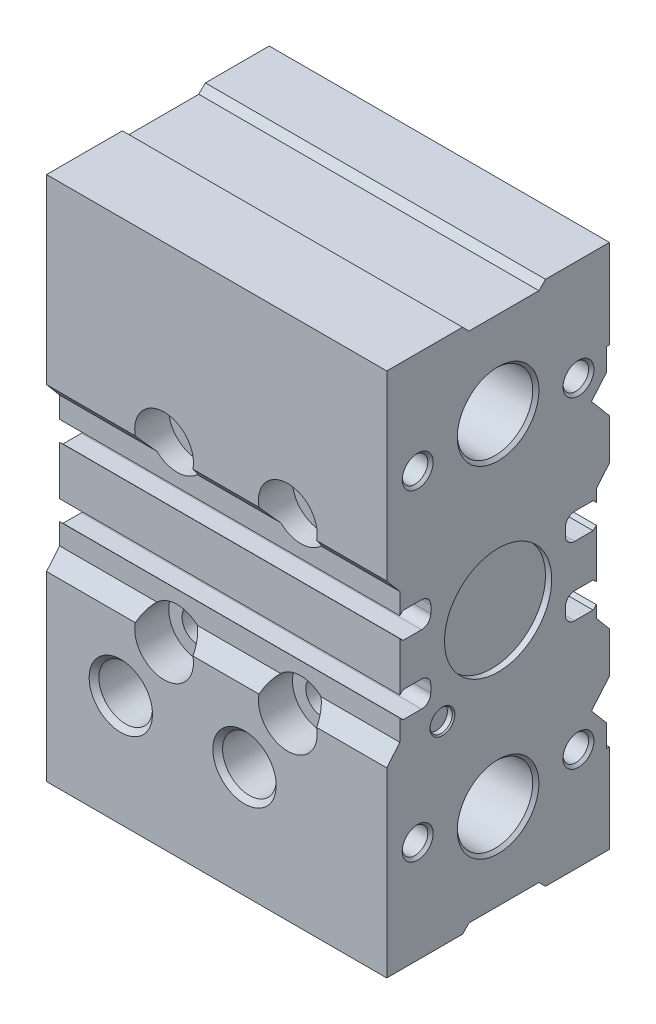
SolidWorks part; units mm, degrees
ref_plane "前视基准面" through (0, 0, 0) normal (0, 0, 1) x (1, 0, 0)
ref_plane "上视基准面" through (0, 0, 0) normal (0, 1, 0) x (1, 0, 0)
ref_plane "右视基准面" through (0, 0, 0) normal (1, 0, 0) x (0, 0, -1)
sketch "草图1" plane through (0, 0, 0) normal (1, 0, 0) x (0, 0, -1)
  line L0 (-18, -42.5) -> (-5.75, -42.5)
  line L1 (-5.75, -42.5) -> (-4.6875, -41.4375)
  line L2 (-4.6875, -41.4375) -> (6.6042, -41.4375)
  line L3 (6.6042, -41.4375) -> (7.6667, -42.5)
  line L4 (7.6667, -42.5) -> (18, -42.5)
  line L5 (18, -42.5) -> (18, -28.1522)
  line L6 (18, -28.1522) -> (17.5, -28.1522)
  line L7 (17.5, -28.1522) -> (17.5, -24.5)
  line L8 (17.5, -24.5) -> (15.1, -21.6667)
  line L9 (15.1, -21.6667) -> (18, -18.2431)
  line L10 (18, -18.2431) -> (18, -11.5959)
  line L11 (18, -11.5959) -> (15.8824, -9.0722)
  line L12 (15.8824, -9.0722) -> (15.8824, -7.1556)
  line L13 (15.3538, -7.6556) -> (12.3824, -7.6556)
  line L14 (10.8824, -6.1556) -> (10.8824, -4.9556)
  line L15 (12.3824, -3.4556) -> (15.3538, -3.4556)
  line L16 (15.8824, -3.9556) -> (15.8824, 3.9556)
  line L17 (15.3538, 3.4556) -> (12.3824, 3.4556)
  line L18 (10.8824, 4.9556) -> (10.8824, 6.1556)
  line L19 (12.3824, 7.6556) -> (15.3538, 7.6556)
  line L20 (15.8824, 7.1556) -> (15.8824, 9.0722)
  line L21 (15.8824, 9.0722) -> (18, 11.5959)
  line L22 (18, 11.5959) -> (18, 18.2431)
  line L23 (18, 18.2431) -> (15.1, 21.6667)
  line L24 (15.1, 21.6667) -> (17.5, 24.5)
  line L25 (17.5, 24.5) -> (17.5, 28.1522)
  line L26 (17.5, 28.1522) -> (18, 28.1522)
  line L27 (18, 28.1522) -> (18, 42.5)
  line L28 (18, 42.5) -> (7.6667, 42.5)
  line L29 (7.6667, 42.5) -> (6.6042, 41.4375)
  line L30 (6.6042, 41.4375) -> (-4.6875, 41.4375)
  line L31 (-4.6875, 41.4375) -> (-5.75, 42.5)
  line L32 (-5.75, 42.5) -> (-18, 42.5)
  line L33 (-18, 42.5) -> (-18, 13.0793)
  line L34 (-18, 13.0793) -> (-15.8824, 10.5556)
  line L35 (-15.8824, 10.5556) -> (-15.8824, 7.1556)
  line L36 (-15.3538, 7.6556) -> (-12.3824, 7.6556)
  line L37 (-10.8824, 6.1556) -> (-10.8824, 4.9556)
  line L38 (-12.3824, 3.4556) -> (-15.3538, 3.4556)
  line L39 (-15.8824, 3.9556) -> (-15.8824, -3.9556)
  line L40 (-15.3538, -3.4556) -> (-12.3824, -3.4556)
  line L41 (-10.8824, -4.9556) -> (-10.8824, -6.1556)
  line L42 (-12.3824, -7.6556) -> (-15.3538, -7.6556)
  line L43 (-15.8824, -7.1556) -> (-15.8824, -10.5556)
  line L44 (-15.8824, -10.5556) -> (-18, -13.0793)
  line L45 (-18, -13.0793) -> (-18, -42.5)
  arc A0 (15.8824, -7.1556) -> (15.3538, -7.6556) centre (13.8681, -5.5556) cw
  arc A1 (12.3824, -7.6556) -> (10.8824, -6.1556) centre (12.3824, -6.1556) cw
  arc A2 (10.8824, -4.9556) -> (12.3824, -3.4556) centre (12.3824, -4.9556) cw
  arc A3 (15.3538, -3.4556) -> (15.8824, -3.9556) centre (13.8681, -5.5556) cw
  arc A4 (15.8824, 3.9556) -> (15.3538, 3.4556) centre (13.8681, 5.5556) cw
  arc A5 (12.3824, 3.4556) -> (10.8824, 4.9556) centre (12.3824, 4.9556) cw
  arc A6 (10.8824, 6.1556) -> (12.3824, 7.6556) centre (12.3824, 6.1556) cw
  arc A7 (15.3538, 7.6556) -> (15.8824, 7.1556) centre (13.8681, 5.5556) cw
  arc A8 (-15.8824, 7.1556) -> (-15.3538, 7.6556) centre (-13.8681, 5.5556) cw
  arc A9 (-12.3824, 7.6556) -> (-10.8824, 6.1556) centre (-12.3824, 6.1556) cw
  arc A10 (-10.8824, 4.9556) -> (-12.3824, 3.4556) centre (-12.3824, 4.9556) cw
  arc A11 (-15.3538, 3.4556) -> (-15.8824, 3.9556) centre (-13.8681, 5.5556) cw
  arc A12 (-15.8824, -3.9556) -> (-15.3538, -3.4556) centre (-13.8681, -5.5556) cw
  arc A13 (-12.3824, -3.4556) -> (-10.8824, -4.9556) centre (-12.3824, -4.9556) cw
  arc A14 (-10.8824, -6.1556) -> (-12.3824, -7.6556) centre (-12.3824, -6.1556) cw
  arc A15 (-15.3538, -7.6556) -> (-15.8824, -7.1556) centre (-13.8681, -5.5556) cw
extrude "凸台-拉伸1" add sketch "草图1" along normal blind 55
sketch "草图2" plane through (0, 0, 0) normal (0, 0, 1) x (1, 0, 0)
  line L0 (0, 27.5) -> (0, 34.1)
  line L1 (0, 34.1) -> (0.5, 33.6)
  line L2 (0.5, 33.6) -> (54.5, 33.6)
  line L3 (54.5, 33.6) -> (55, 34.1)
  line L4 (55, 34.1) -> (55, 27.5)
  line L5 (55, 27.5) -> (0, 27.5)
  line L6 (55, 27.5) -> (0, 27.5) construction
revolve "切除-旋转1" cut sketch "草图2" angle 360 about L6 reverse direction yes
sketch "草图3" plane through (0, 0, 0) normal (0, 0, 1) x (1, 0, 0)
  line L0 (0, -27.5) -> (0, -20.9)
  line L1 (0, -20.9) -> (0.5, -21.4)
  line L2 (0.5, -21.4) -> (54.5, -21.4)
  line L3 (54.5, -21.4) -> (55, -20.9)
  line L4 (55, -20.9) -> (55, -27.5)
  line L5 (55, -27.5) -> (0, -27.5)
  line L6 (55, -27.5) -> (0, -27.5) construction
revolve "切除-旋转2" cut sketch "草图3" angle 360 about L6 reverse direction yes
ref_plane "基准面4" through (0, 14, 0) normal (0, 1, 0) x (1, 0, 0)
ref_plane "基准面5" through (0, 0, 18) normal (0, 0, 1) x (1, 0, 0)
sketch "草图4" plane through (0, 14, 0) normal (0, 1, 0) x (1, 0, 0)
  line L0 (39, 18) -> (41.5, 18)
  line L1 (41.5, 18) -> (41.067, 17.567)
  line L2 (41.067, 17.567) -> (41.067, 4.733)
  line L3 (41.067, 4.733) -> (41.6, 4.2)
  line L4 (41.6, 4.2) -> (41.6, -12.5)
  line L5 (41.6, -12.5) -> (43.75, -12.5)
  line L6 (43.75, -12.5) -> (43.75, -18)
  line L7 (43.75, -18) -> (39, -18)
  line L8 (39, -18) -> (39, 18)
  line L9 (39, -18) -> (39, 18) construction
revolve "切除-旋转3" cut sketch "草图4" angle 360 about L9 reverse direction yes
cosmetic thread "装饰螺纹线1" parameters "D1"=12, "D2"=5
sketch "草图5" plane through (0, 0, 0) normal (0, 0, 1) x (1, 0, 0)
  line L0 (39, 14) -> (-961, 14)
  line L1 (39, 14) -> (39, -986)
pattern_linear "阵列(线性)1" count 2 spacing 20 along (-1, 0, 0) count 2 spacing 28 along (0, -1, 0) of "切除-旋转3"
ref_plane "基准面6" through (0, 32, 0) normal (0, 1, 0) x (1, 0, 0)
sketch "草图6" plane through (0, 32, 0) normal (0, 1, 0) x (1, 0, 0)
  line L0 (11, 18) -> (13.5, 18)
  line L1 (13.5, 18) -> (13.067, 17.567)
  line L2 (13.067, 17.567) -> (13.067, 4.1934)
  line L3 (13.067, 4.1934) -> (11, 3)
  line L4 (11, 3) -> (11, 18)
  line L5 (11, 3) -> (11, 18) construction
revolve "切除-旋转4" cut sketch "草图6" angle 360 about L5 reverse direction yes
cosmetic thread "装饰螺纹线2" parameters "D1"=12, "D2"=5
ref_plane "基准面7" through (0, 0, -18) normal (0, 0, 1) x (1, 0, 0)
sketch "草图7" plane through (0, 0, 0) normal (0, 0, 1) x (1, 0, 0)
  line L0 (11, 32) -> (1011, 32)
  line L1 (11, 32) -> (11, -968)
pattern_linear "阵列(线性)2" count 2 spacing 30 along (1, 0, 0) count 2 spacing 64 along (0, -1, 0) of "切除-旋转4"
ref_plane "基准面8" through (0, -24.5, 0) normal (0, 1, 0) x (1, 0, 0)
sketch "草图8" plane through (0, -24.5, 0) normal (0, 1, 0) x (1, 0, 0)
  line L0 (12, -6.5696) -> (16.0744, -8.922)
  line L1 (16.0744, -8.922) -> (16.3335, -17.2124)
  line L2 (16.3335, -17.2124) -> (17.1211, -18)
  line L3 (17.1211, -18) -> (12, -18)
  line L4 (12, -18) -> (12, -6.5696)
  line L5 (12, -18) -> (12, -6.5696) construction
revolve "切除-旋转5" cut sketch "草图8" angle 360 about L5 reverse direction yes
sketch "草图9" plane through (0, -24.5, 0) normal (0, 1, 0) x (1, 0, 0)
  line L0 (32, -6.5696) -> (36.0744, -8.922)
  line L1 (36.0744, -8.922) -> (36.3335, -17.2124)
  line L2 (36.3335, -17.2124) -> (37.1211, -18)
  line L3 (37.1211, -18) -> (32, -18)
  line L4 (32, -18) -> (32, -6.5696)
  line L5 (32, -18) -> (32, -6.5696) construction
revolve "切除-旋转6" cut sketch "草图9" angle 360 about L5 reverse direction yes
sketch "草图10" plane through (0, 0, 0) normal (0, 1, 0) x (1, 0, 0)
  line L0 (0, 0) -> (0, 5.1)
  line L1 (0, 5.1) -> (20, 5.1)
  line L2 (20, 5.1) -> (20, 0)
  line L3 (20, 0) -> (0, 0)
  line L4 (20, 0) -> (0, 0) construction
revolve "切除-旋转7" cut sketch "草图10" angle 360 about L4 reverse direction yes
sketch "草图11" plane through (0, 0, 0) normal (0, 1, 0) x (1, 0, 0)
  line L0 (54, 0) -> (54, 8.6667)
  line L1 (54, 8.6667) -> (55, 8.6667)
  line L2 (55, 8.6667) -> (55, 0)
  line L3 (55, 0) -> (54, 0)
  line L4 (55, 0) -> (54, 0) construction
revolve "切除-旋转8" cut sketch "草图11" angle 360 about L4 reverse direction yes
ref_plane "基准面9" through (12, 0, 0) normal (1, 0, 0) x (0, 0, -1)
sketch "草图12" plane through (12, 0, 0) normal (1, 0, 0) x (0, 0, -1)
  line L0 (-11.5, -31.0696) -> (-7.4256, -33.422)
  line L1 (-7.4256, -33.422) -> (-7.1665, -41.7124)
  line L2 (-7.1665, -41.7124) -> (-6.3789, -42.5)
  line L3 (-6.3789, -42.5) -> (-11.5, -42.5)
  line L4 (-11.5, -42.5) -> (-11.5, -31.0696)
  line L5 (-11.5, -42.5) -> (-11.5, -31.0696) construction
revolve "切除-旋转9" cut sketch "草图12" angle 360 about L5 reverse direction yes
ref_plane "基准面10" through (32, 0, 0) normal (1, 0, 0) x (0, 0, -1)
sketch "草图13" plane through (32, 0, 0) normal (1, 0, 0) x (0, 0, -1)
  line L0 (-11.5, -31.0696) -> (-7.4256, -33.422)
  line L1 (-7.4256, -33.422) -> (-7.1665, -41.7124)
  line L2 (-7.1665, -41.7124) -> (-6.3789, -42.5)
  line L3 (-6.3789, -42.5) -> (-11.5, -42.5)
  line L4 (-11.5, -42.5) -> (-11.5, -31.0696)
  line L5 (-11.5, -42.5) -> (-11.5, -31.0696) construction
revolve "切除-旋转10" cut sketch "草图13" angle 360 about L5 reverse direction yes
ref_plane "基准面11" through (0, -11.0638, 0) normal (0, 1, 0) x (1, 0, 0)
sketch "草图14" plane through (0, -11.0638, 0) normal (0, 1, 0) x (1, 0, 0)
  line L0 (54, -9) -> (54, -7.2)
  line L1 (54, -7.2) -> (54.8, -7.2)
  line L2 (54.8, -7.2) -> (55, -7)
  line L3 (55, -7) -> (55, -9)
  line L4 (55, -9) -> (54, -9)
  line L5 (55, -9) -> (54, -9) construction
revolve "切除-旋转11" cut sketch "草图14" angle 360 about L5 reverse direction yes
ref_plane "基准面12" through (0, 26, 0) normal (0, 1, 0) x (1, 0, 0)
sketch "草图15" plane through (0, 26, 0) normal (0, 1, 0) x (1, 0, 0)
  line L0 (39.4, 13) -> (40.5934, 15.067)
  line L1 (40.5934, 15.067) -> (54.567, 15.067)
  line L2 (54.567, 15.067) -> (55, 15.5)
  line L3 (55, 15.5) -> (55, 13)
  line L4 (55, 13) -> (39.4, 13)
  line L5 (55, 13) -> (39.4, 13) construction
revolve "切除-旋转12" cut sketch "草图15" angle 360 about L5 reverse direction yes
cosmetic thread "装饰螺纹线3" parameters "D1"=13, "D2"=5
sketch "草图16" plane through (0, 26, 0) normal (0, 1, 0) x (1, 0, 0)
  line L0 (39.4, -13) -> (40.5934, -10.933)
  line L1 (40.5934, -10.933) -> (54.567, -10.933)
  line L2 (54.567, -10.933) -> (55, -10.5)
  line L3 (55, -10.5) -> (55, -13)
  line L4 (55, -13) -> (39.4, -13)
  line L5 (55, -13) -> (39.4, -13) construction
revolve "切除-旋转13" cut sketch "草图16" angle 360 about L5 reverse direction yes
cosmetic thread "装饰螺纹线4" parameters "D1"=13, "D2"=5
ref_plane "基准面13" through (0, -26, 0) normal (0, 1, 0) x (1, 0, 0)
sketch "草图17" plane through (0, -26, 0) normal (0, 1, 0) x (1, 0, 0)
  line L0 (39.4, 13) -> (40.5934, 15.067)
  line L1 (40.5934, 15.067) -> (54.567, 15.067)
  line L2 (54.567, 15.067) -> (55, 15.5)
  line L3 (55, 15.5) -> (55, 13)
  line L4 (55, 13) -> (39.4, 13)
  line L5 (55, 13) -> (39.4, 13) construction
revolve "切除-旋转14" cut sketch "草图17" angle 360 about L5 reverse direction yes
cosmetic thread "装饰螺纹线5" parameters "D1"=13, "D2"=5
sketch "草图18" plane through (0, -26, 0) normal (0, 1, 0) x (1, 0, 0)
  line L0 (39.4, -13) -> (40.5934, -10.933)
  line L1 (40.5934, -10.933) -> (54.567, -10.933)
  line L2 (54.567, -10.933) -> (55, -10.5)
  line L3 (55, -10.5) -> (55, -13)
  line L4 (55, -13) -> (39.4, -13)
  line L5 (55, -13) -> (39.4, -13) construction
revolve "切除-旋转15" cut sketch "草图18" angle 360 about L5 reverse direction yes
cosmetic thread "装饰螺纹线6" parameters "D1"=13, "D2"=5
ref_plane "B XY" through (0, 0, 0) normal (1, 0, 0) x (0, 0, -1)
ref_plane "B XZ" through (0, 0, 0) normal (0, -1, 0) x (-1, 0, 0)
ref_plane "B YZ" through (0, 0, 0) normal (0, 0, -1) x (-1, 0, 0)
ref_axis "B X" through (0, 0, 80.9) along (0, 0, -1)
ref_axis "B Y" through (0, -50, 0) along (0, 1, 0)
ref_axis "B Z" through (80.9, 0, 0) along (-1, 0, 0)
sketch3d "B"
  point P0 (0, 0, 0)
